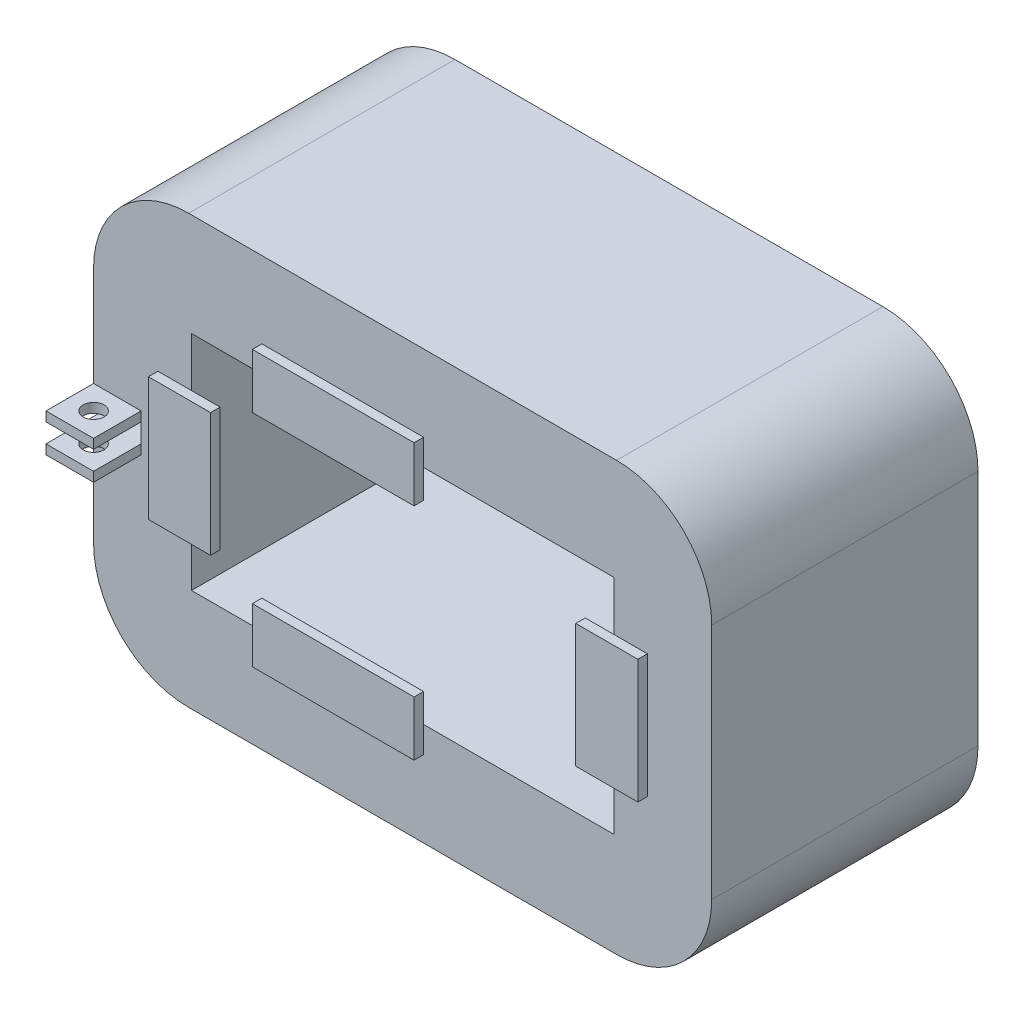
SolidWorks part; units mm, degrees
ref_plane "前基準面" through (0, 0, 0) normal (0, 0, 1) x (1, 0, 0)
ref_plane "上基準面" through (0, 0, 0) normal (0, 1, 0) x (1, 0, 0)
ref_plane "右基準面" through (0, 0, 0) normal (1, 0, 0) x (0, 0, -1)
sketch "草圖1" plane through (0, 0, 0) normal (0, 0, 1) x (1, 0, 0)
  line L0 (-9.02, 0) -> (7.9922, 0) construction
  line L2 (-59.9347, 22.5) -> (5.0653, 22.5)
  line L3 (-59.9347, 22.5) -> (-59.9347, -22.5)
  line L4 (-59.9347, -22.5) -> (5.0653, -22.5)
  line L5 (5.0653, 22.5) -> (5.0653, -22.5)
  dimension "D1" = 45
  dimension "D2" = 22.5
  dimension "D3" = 65
extrude "填料-伸長1" add sketch "草圖1" along normal blind 28
sketch "草圖2" plane through (0, 0, 0) normal (0, 0, 1) x (1, 0, 0)
  line L0 (-59.9347, 0) -> (5.361, 0) construction
  line L1 (-59.9347, 22.5) -> (-59.9347, -22.5) construction
  line L2 (-27.4347, 22.5) -> (-27.4347, -22.5) construction
  line L3 (5.0653, 22.5) -> (-59.9347, 22.5) construction
  line L4 (-59.9347, -22.5) -> (5.0653, -22.5) construction
  line L6 (-49.6347, 11.7) -> (-5.2347, 11.7)
  line L7 (-49.6347, 11.7) -> (-49.6347, -11.7)
  line L8 (-49.6347, -11.7) -> (-5.2347, -11.7)
  line L9 (-5.2347, 11.7) -> (-5.2347, -11.7)
  dimension "D1" = 44.4
  dimension "D2" = 23.4
  dimension "D3" = 10.3
  dimension "D4" = 10.8
extrude "除料-伸長1" cut sketch "草圖2" along normal blind 39
ref_plane "平面1" through (0, 0, 28) normal (0, 0, 1) x (1, 0, 0)
sketch "草圖3" plane through (0, 0, 28) normal (0, 0, 1) x (1, 0, 0)
  line L0 (-59.9347, 22.5) -> (-59.9347, -22.5) construction
  line L2 (-59.9347, 12) -> (-55.9347, 12)
  line L3 (-59.9347, 12) -> (-59.9347, -12)
  line L4 (-59.9347, -12) -> (-55.9347, -12)
  line L5 (-55.9347, 12) -> (-55.9347, -12)
  line L8 (-5.2347, -11.7) -> (-49.6347, -11.7) construction
  dimension "D1" = 4
  dimension "D2" = 24
  dimension "D3" = 0.3
ref_plane "平面2" through (-59.9347, 0, 0) normal (-1, 0, 0) x (0, 0, 1)
sketch "草圖6" plane through (0, 0, 28) normal (0, 0, 1) x (1, 0, 0)
  line L0 (-15.2347, 0.3) -> (5.0653, -22.5)
  line L1 (-5.2347, 11.7) -> (-5.2347, -11.7) construction
  line L2 (-5.2347, -11.7) -> (-49.6347, -11.7) construction
  line L3 (-15.2347, 0.3) -> (-15.2347, -22.5)
  line L4 (-59.9347, -22.5) -> (5.0653, -22.5) construction
  line L5 (-15.2347, -22.5) -> (5.0653, -22.5)
  dimension "D1" = 10
  dimension "D2" = 12
ref_plane "平面4" through (0, 0, 0) normal (0, 0, -1) x (-1, 0, 0)
fillet "圓角1" radius 10 1 edges at (-59.9347, -22.5, 14) type face fillet first side face at (-59.9347, 0, 14) second side face at (-27.4347, -22.5, 14)
fillet "圓角2" radius 10 1 edges at (-59.9347, 22.5, 14) type face fillet first side face at (-27.4347, 22.5, 14) second side face at (-59.9347, 5, 14)
fillet "圓角3" radius 10 1 edges at (5.0653, 22.5, 14) type face fillet first side face at (-22.4347, 22.5, 14) second side face at (5.0653, 0, 14)
fillet "圓角4" radius 10 1 edges at (5.0653, -22.5, 14) type face fillet first side face at (-22.4347, -22.5, 14) second side face at (5.0653, -5, 14)
ref_plane "平面6" through (0, 0, 29) normal (0, 0, 1) x (1, 0, 0)
sketch "草圖10" plane through (0, 0, 29) normal (0, 0, 1) x (1, 0, 0)
  line L6 (-49.6347, 0) -> (-4.2092, 0) construction
  line L7 (-49.6347, -11.7) -> (-49.6347, 11.7) construction
  line L8 (-27.4347, -11.7) -> (-27.4347, 19.297) construction
  line L9 (-5.2347, -11.7) -> (-49.6347, -11.7) construction
  line L11 (-49.6347, 6.5) -> (-53.1651, 6.5)
  line L14 (-53.1651, 6.5) -> (-53.1651, -6.5)
  line L17 (-49.6347, 6.5) -> (-46.6347, 6.5)
  line L18 (-46.6347, 6.5) -> (-46.6347, -6.5)
  line L20 (-42.2347, -11.7) -> (-42.2347, -8.7)
  line L25 (-42.2347, -11.7) -> (-42.2347, -14.4546)
  line L27 (-8.2347, 6.5) -> (-8.2347, -6.5)
  line L28 (-8.2347, -6.5) -> (-5.2347, -6.5)
  line L29 (-5.2347, -6.5) -> (-1.7043, -6.5)
  line L30 (-1.7043, 6.5) -> (-1.7043, -6.5)
  line L32 (-25.2347, 8.7) -> (-25.2347, 14.4546)
  line L33 (-25.2347, -14.4546) -> (-25.2347, -8.7)
  line L34 (-25.2347, -14.4546) -> (-42.2347, -14.4546)
  line L35 (-25.2347, -8.7) -> (-42.2347, -8.7)
  line L36 (-25.2347, 8.7) -> (-42.2347, 8.7)
  line L37 (-25.2347, 14.4546) -> (-42.2347, 14.4546)
  line L38 (-42.2347, 8.7) -> (-42.2347, 14.4546)
  line L39 (-46.6347, -6.5) -> (-53.1651, -6.5)
  line L40 (-1.7043, 6.5) -> (-8.2347, 6.5)
  dimension "D3" = 13
  dimension "D4" = 6.5
extrude "填料-伸長6" add sketch "草圖10" against normal blind 1 separate body
sketch "草圖19" plane through (0, 0, 0) normal (0, 1, 0) x (1, 0, 0)
  line L0 (-59.9347, 13.75) -> (-59.9347, -13.75) construction
  line L1 (-59.9347, 1.0971) -> (-54.9347, 1.0971)
  line L2 (-59.9347, 1.0971) -> (-59.9347, -29)
  line L3 (-59.9347, -29) -> (-54.9347, -29)
  line L4 (-54.9347, 1.0971) -> (-54.9347, -29)
  line L5 (-24.75, -29) -> (24.75, -29) construction
  dimension "D1" = 5
extrude "除料-伸長3" cut sketch "草圖19" against normal blind 1 and the other way blind 1
sketch "草圖20" plane through (0, 0, 0) normal (0, 0, 1) x (1, 0, 0)
  line L0 (-62.8384, 0) -> (-42.2222, 0) construction
  line L1 (-59.9347, 1) -> (-54.9347, 1)
  line L2 (-59.9347, 1) -> (-59.9347, 2)
  line L3 (-59.9347, 2) -> (-54.9347, 2)
  line L4 (-54.9347, 1) -> (-54.9347, 2)
  line L5 (15.95, 0) -> (-15.95, 0) construction
  line L6 (-54.9347, -1) -> (-54.9347, -2)
  line L7 (-59.9347, -2) -> (-54.9347, -2)
  line L8 (-59.9347, -1) -> (-54.9347, -1)
  line L9 (-59.9347, -1) -> (-59.9347, -2)
  dimension "D1" = 5
  dimension "D2" = 1
extrude "填料-伸長12" add sketch "草圖20" against normal blind 5
sketch "草圖21" plane through (0, 0, 28) normal (0, 0, 1) x (1, 0, 0)
  line L0 (-62.4066, 0) -> (-44.8127, 0) construction
  line L1 (-59.9347, 1) -> (-54.9347, 1)
  line L2 (-59.9347, 1) -> (-59.9347, 2)
  line L3 (-59.9347, 2) -> (-54.9347, 2)
  line L4 (-54.9347, 1) -> (-54.9347, 2)
  line L5 (18.7, 0) -> (-18.7, 0) construction
  line L6 (-54.9347, -1) -> (-54.9347, -2)
  line L7 (-59.9347, -1) -> (-54.9347, -1)
  line L8 (-59.9347, -1) -> (-59.9347, -2)
  line L9 (-59.9347, -2) -> (-54.9347, -2)
  dimension "D1" = 1
extrude "填料-伸長13" add sketch "草圖21" along normal blind 5
sketch "草圖22" plane through (0, 0, 0) normal (0, 1, 0) x (1, 0, 0)
  line L0 (-57.4347, 5) -> (-57.4347, -36.775) construction
  line L1 (-54.9347, 5) -> (-59.9347, 5) construction
  line L2 (-54.9347, 2.5) -> (-59.9347, 2.5) construction
  line L3 (-54.9347, 5) -> (-54.9347, 0) construction
  line L4 (-59.9347, 6.325) -> (-59.9347, -6.325) construction
  line L5 (-54.9347, -30.5) -> (-59.9347, -30.5) construction
  line L6 (-54.9347, -33) -> (-54.9347, -28) construction
  circle A0 centre (-57.4347, -30.5) radius 1.1
  circle A1 centre (-57.4347, 2.5) radius 1.1
  dimension "D1" = 2.2
  dimension "D2" = 2.2
extrude "除料-伸長4" cut sketch "草圖22" against normal blind 5 and the other way blind 5
